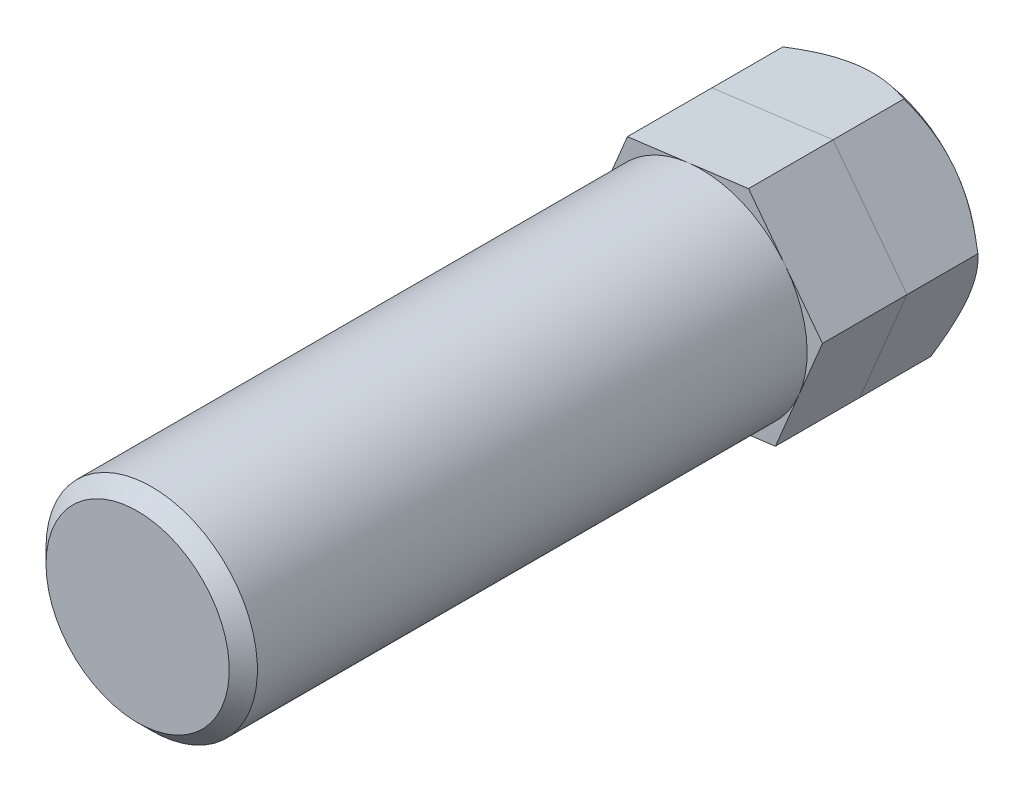
SolidWorks part; units mm, degrees
ref_plane "Front Plane" through (0, 0, 0) normal (0, 0, 1) x (1, 0, 0)
ref_plane "Top Plane" through (0, 0, 0) normal (0, 1, 0) x (1, 0, 0)
ref_plane "Right Plane" through (0, 0, 0) normal (1, 0, 0) x (0, 0, -1)
sketch "Sketch1" plane through (0, 0, 0) normal (0, 1, 0) x (1, 0, 0)
  line L1 (7.5, 40) -> (0, 40)
  line L2 (7.5, 40) -> (7.5, 0)
  line L3 (7.5, 0) -> (0, 0)
  line L4 (0, 40) -> (0, 0)
  line L5 (7.5, 40) -> (0, 0) construction
  line L6 (7.5, 0) -> (0, 40) construction
  point P0 (3.75, 20)
  dimension "D1" = 40
  dimension "D2" = 7.5
revolve "Revolve1" add sketch "Sketch1" angle 360 about L4
sketch "Sketch2" plane through (0, 0, -40) normal (0, 0, -1) x (-1, 0, 0)
  line L1 (-3.3412, 7.9898) -> (-8.5899, 1.1013)
  line L2 (-8.5899, 1.1013) -> (-5.2488, -6.8884)
  line L3 (-5.2488, -6.8884) -> (3.3412, -7.9898)
  line L4 (3.3412, -7.9898) -> (8.5899, -1.1013)
  line L5 (8.5899, -1.1013) -> (5.2488, 6.8884)
  line L6 (5.2488, 6.8884) -> (-3.3412, 7.9898)
  circle A0 centre (0, 0) radius 7.5 construction
  circle A1 centre (0, 0) radius 7.5 construction
extrude "Boss-Extrude1" add sketch "Sketch2" along normal blind 6
sketch "Sketch3" plane through (0, 0, -46) normal (0, 0, -1) x (-1, 0, 0)
  line L6 (5.2488, 6.8884) -> (-3.3412, 7.9898)
  line L7 (-3.3412, 7.9898) -> (-8.5899, 1.1013)
  line L8 (-8.5899, 1.1013) -> (-5.2488, -6.8884)
  line L9 (-5.2488, -6.8884) -> (3.3412, -7.9898)
  line L10 (3.3412, -7.9898) -> (8.5899, -1.1013)
  line L11 (8.5899, -1.1013) -> (5.2488, 6.8884)
  line L12 (5.2488, 6.8884) -> (-3.3412, 7.9898)
  line L13 (-3.3412, 7.9898) -> (-8.5899, 1.1013)
  line L14 (-8.5899, 1.1013) -> (-5.2488, -6.8884)
  line L15 (-5.2488, -6.8884) -> (3.3412, -7.9898)
  line L16 (3.3412, -7.9898) -> (8.5899, -1.1013)
  line L17 (8.5899, -1.1013) -> (5.2488, 6.8884)
  dimension "D1" = 0
extrude "Boss-Extrude2" add sketch "Sketch3" along normal blind 6 separate body
sketch "Sketch4" plane through (0, 0, -52) normal (0, 0, -1) x (-1, 0, 0)
  line L0 (5.2488, 6.8884) -> (-3.3412, 7.9898) construction
  circle A0 centre (0, 0) radius 7.5
extrude "Cut-Extrude1" cut sketch "Sketch4" against normal blind 2 draft 50 flip side to cut
chamfer "Chamfer1" distance 1 angle 45 1 edges at (-7.5, 0, 0)
ref_axis "Axis1" through (0, 0, -1) along (0, 0, -1)
